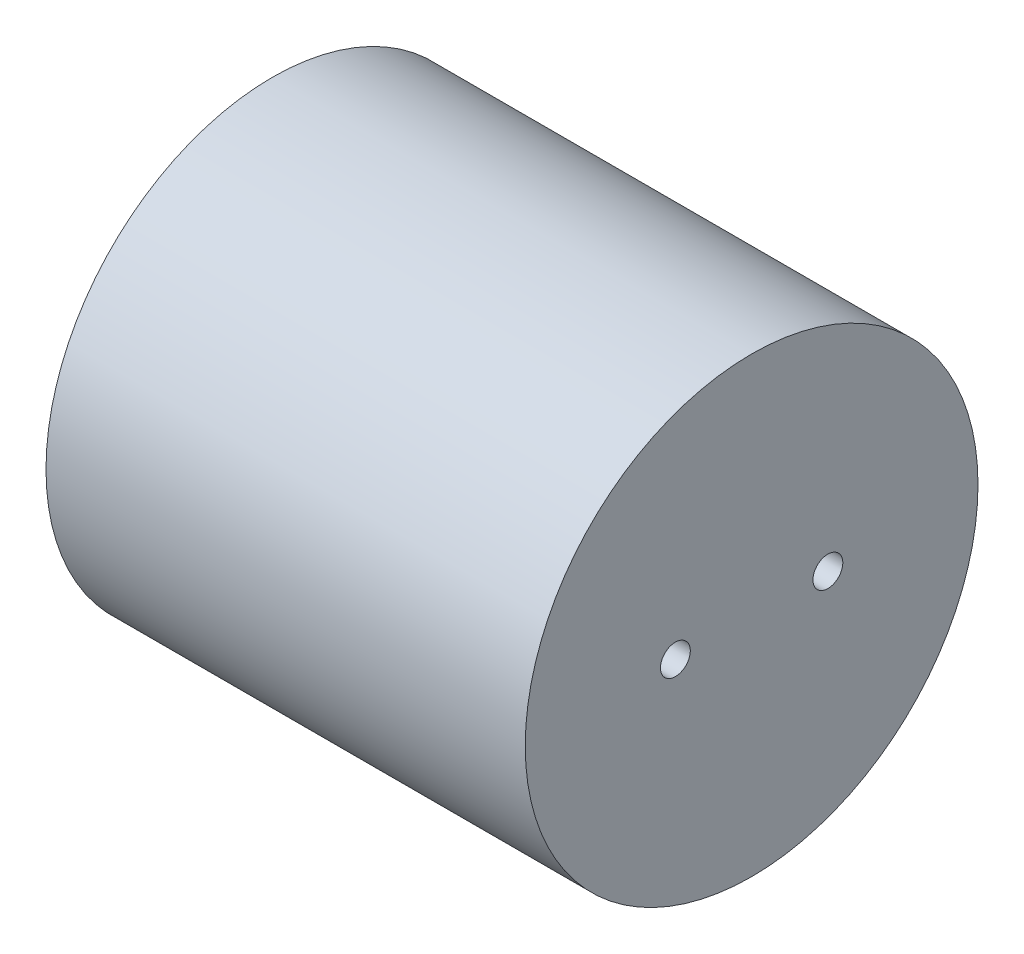
SolidWorks part; units mm, degrees
ref_plane "Front Plane" through (0, 0, 0) normal (0, 0, 1) x (1, 0, 0)
ref_plane "Top Plane" through (0, 0, 0) normal (0, 1, 0) x (1, 0, 0)
ref_plane "Right Plane" through (0, 0, 0) normal (1, 0, 0) x (0, 0, -1)
sketch "Sketch2" plane through (0, 0, 0) normal (1, 0, 0) x (0, 0, -1)
  circle A0 centre (0, 0) radius 49.4919
  dimension "D1" = 98.9838
extrude "Boss-Extrude1" add sketch "Sketch2" along normal blind 104.775
sketch "Sketch3" plane through (0, 0, 0) normal (-1, 0, 0) x (0, 0, 1)
  line L1 (-27.7813, -11.1125) -> (27.7812, -11.1125)
  line L2 (-27.7813, -11.1125) -> (-27.7813, 11.1125)
  line L3 (-27.7813, 11.1125) -> (27.7812, 11.1125)
  line L4 (27.7812, -11.1125) -> (27.7812, 11.1125)
  line L5 (-27.7813, -11.1125) -> (27.7812, 11.1125) construction
  line L6 (-27.7813, 11.1125) -> (27.7812, -11.1125) construction
  point P0 (0, 0)
  dimension "D1" = 22.225
  dimension "D2" = 55.5625
extrude "Cut-Extrude1" cut sketch "Sketch3" against normal blind 88.9
hole_wizard "5/16-18 Tapped Hole1" positions "Sketch4" profile "Sketch5" tap size "5/16-18" standard "ANSI Inch" end condition through all
sketch "Sketch4" plane through (88.9, 0, 0) normal (-1, 0, 0) x (0, 0, 1)
  line L0 (0, 0) -> (0, 38.6829) construction
  point P0 (-16.6687, 0)
  point P7 (0, 0)
  point P8 (16.6687, 0)
  point P9 (0, 0)
  dimension "D1" = 33.3375
sketch "Sketch5" plane through (88.9, 0, -16.6687) normal (0, 1, 0) x (0, 0, 1)
  line L0 (0, 0) -> (0, 15.875)
  line L1 (0, 15.875) -> (3.2639, 15.875)
  line L2 (3.2639, 15.875) -> (3.2639, 0)
  line L5 (3.2639, 0) -> (0, 0)
  line L11 (0, -6.35) -> (0, 107.95) construction
  dimension "Thru Tap Drill Dia." = 6.5278
  dimension "Thru Tap Drill Depth" = 15.875
hole_wizard "1/4-20 Tapped Hole1" positions "Sketch6" profile "Sketch7" tap size "1/4-20" standard "ANSI Inch"
sketch "Sketch6" plane through (0, 0, 0) normal (-1, 0, 0) x (0, 0, 1)
  line L5 (0, 0) -> (0, 33.6343) construction
  line L7 (0, 0) -> (-27.7813, 0) construction
  line L8 (-27.7813, 11.1125) -> (-27.7813, -11.1125) construction
  point P0 (-22.225, 22.225)
  point P34 (0, 0)
  point P35 (-22.225, -22.225)
  point P36 (0, 0)
  point P37 (22.225, -22.225)
  point P38 (22.225, 22.225)
  dimension "D1" = 44.45
  dimension "D2" = 44.45
sketch "Sketch7" plane through (0, 22.225, -22.225) normal (0, 1, 0) x (0, 0, 1)
  line L0 (0, 0) -> (0, 77.7338)
  line L1 (0, 77.7338) -> (2.5527, 76.2)
  line L2 (2.5527, 76.2) -> (2.5527, 0)
  line L5 (2.5527, 0) -> (0, 0)
  line L10 (0, 77.7338) -> (-2.5527, 76.2) construction
  line L11 (0, -6.35) -> (0, 107.95) construction
  dimension "Tap Drill Dia." = 5.1054
  dimension "Tap Drill Depth" = 76.2
  dimension "Drill Angle" = 118
